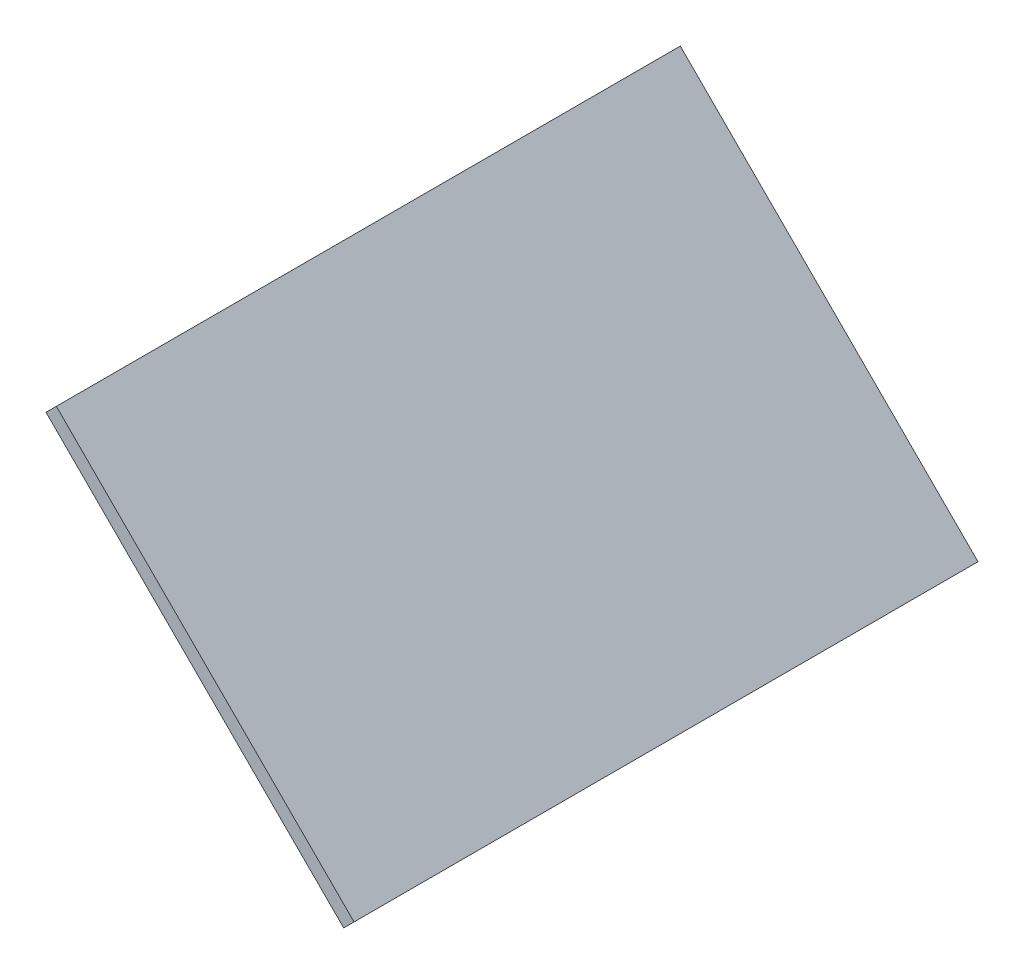
SolidWorks part; units mm, degrees
material "Pine"
ref_plane "Front Plane" through (0, 0, 0) normal (0, 0, 1) x (1, 0, 0)
ref_plane "Top Plane" through (0, 0, 0) normal (0, 1, 0) x (1, 0, 0)
ref_plane "Right Plane" through (0, 0, 0) normal (1, 0, 0) x (0, 0, -1)
sketch "Sketch1" plane through (0, 0, 0) normal (0, 0, 1) x (1, 0, 0)
  line L0 (-126.8141, 1469.6159) -> (-514.6154, 1857.4172)
  line L1 (-514.6154, 1857.4172) -> (-528.0858, 1843.9468)
  line L2 (-528.0858, 1843.9468) -> (-525.2525, 1842.8053)
  line L3 (-126.8141, 1469.6159) -> (-140.2845, 1456.1455)
  line L23 (-140.2845, 1456.1455) -> (-528.0858, 1843.9468)
  dimension "D1" = 19.05
extrude "Boss-Extrude1" add sketch "Sketch1" along normal blind 812.8 contours L23 L3 L0 L1 region at (-327.4499, 1656.7813, 0)
